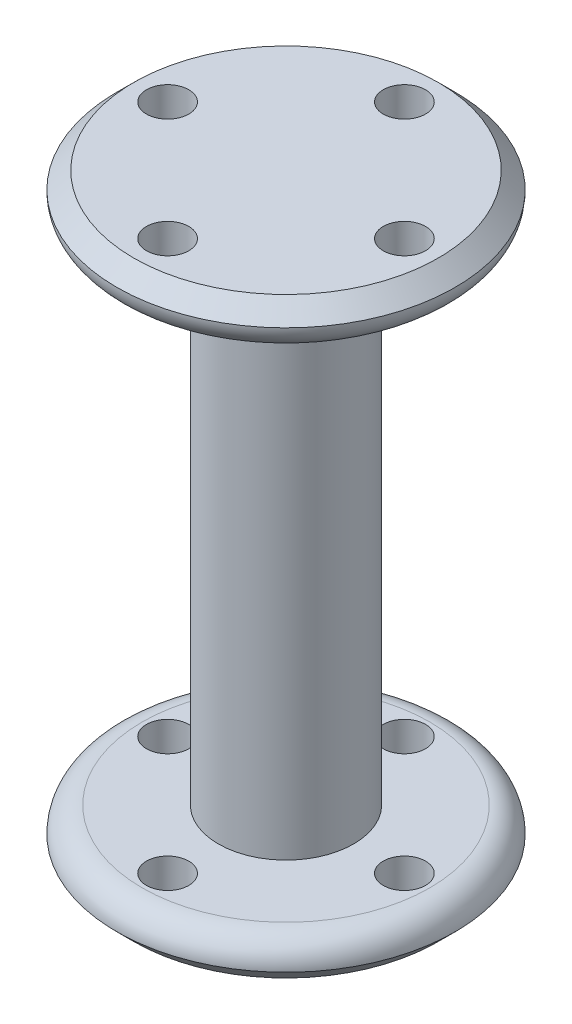
SolidWorks part; units mm, degrees
ref_plane "Front Plane" through (0, 0, 0) normal (0, 0, 1) x (1, 0, 0)
ref_plane "Top Plane" through (0, 0, 0) normal (0, 1, 0) x (1, 0, 0)
ref_plane "Right Plane" through (0, 0, 0) normal (1, 0, 0) x (0, 0, -1)
sketch "Sketch1" plane through (0, 0, 0) normal (0, 1, 0) x (1, 0, 0)
  circle A0 centre (0, 0) radius 8
  dimension "ShaftDiameter" = 16
extrude "Boss-Extrude1" add sketch "Sketch1" along normal mid plane 60 contours A0
sketch "Sketch3" plane through (0, 30, 0) normal (0, 1, 0) x (1, 0, 0)
  circle A0 centre (0, 0) radius 20
  dimension "CapDiameter" = 40
extrude "Boss-Extrude2" add sketch "Sketch3" along normal blind 5 contours A0
chamfer "Chamfer1" distance 2 angle 45 1 edges at (0, 35, 20)
sketch "Sketch4" plane through (0, 35, 0) normal (0, 1, 0) x (1, 0, 0)
  line L0 (0, 20) -> (0, 8) construction
  circle A0 centre (0, 0) radius 20 construction
  circle A1 centre (0, 0) radius 8 construction
  circle A2 centre (0, 14) radius 2.5
  dimension "D1" = 5
extrude "Cut-Extrude1" cut sketch "Sketch4" against normal through all
pattern_circular "CirPattern1" count 4 over 360 about axis through (0, 0, 0) along (0, 1, 0) of "Cut-Extrude1"
fillet "Fillet1" radius 3 1 edges at (0, 30, 20)
hole_wizard "CBORE for #12 Binding Head Machine Screw1" [suppressed] positions "Sketch5" profile "Sketch6" counterbore size "#12" standard "ANSI Inch"
sketch "Sketch5" plane through (0, 55, 0) normal (0, 1, 0) x (1, 0, 0)
  point P0 (0, 0)
sketch "Sketch6" plane through (0, 55, 0) normal (1, 0, 0) x (0, 0, 1)
  line L0 (0, 0) -> (0, 110)
  line L1 (0, 110) -> (2.8956, 110)
  line L3 (2.8956, 110) -> (2.8956, 3.5814)
  line L4 (5.9538, 3.5814) -> (2.8956, 3.5814)
  line L5 (5.9538, 3.5814) -> (5.9538, 0.635)
  line L6 (5.9538, 0.635) -> (6.5888, 0)
  line L7 (6.5888, 0) -> (0, 0)
  line L8 (-5.9538, 0.635) -> (-6.5888, 0) construction
  line L11 (0, -6.35) -> (0, 107.95) construction
  dimension "Thru Hole Dia." = 5.7912
  dimension "Thru Hole Depth" = 110
  dimension "C'Bore Dia." = 11.9075
  dimension "C'Bore Depth" = 3.5814
  dimension "Near C'Sink Dia." = 13.1775
  dimension "Near C'Sink Angle" = 90
mirror "Mirror1" about plane through (0, 0, 0) normal (0, 1, 0) of "CirPattern1", "Chamfer1", "Boss-Extrude2", "Cut-Extrude1", "Fillet1", "CBORE for #12 Binding Head Machine Screw1"
